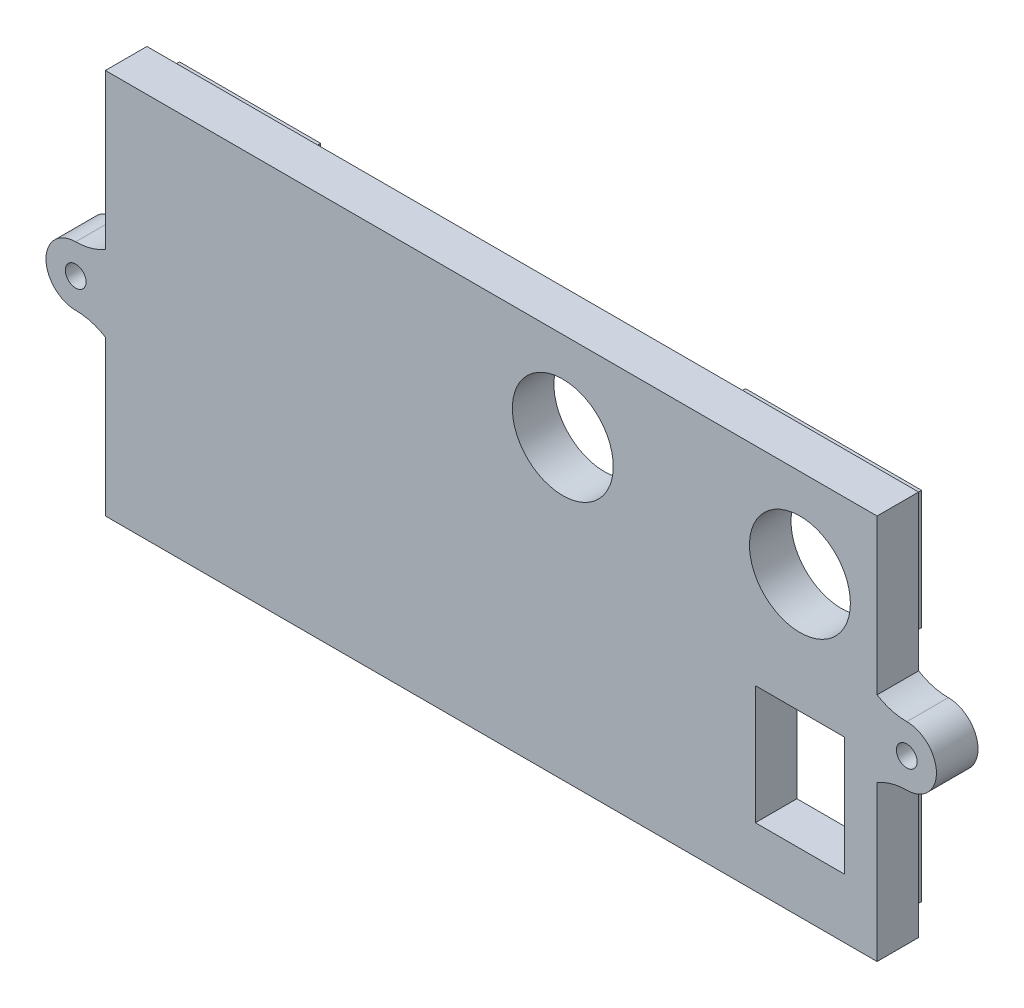
SolidWorks part; units mm, degrees
ref_plane "Front Plane" through (0, 0, 0) normal (0, 0, 1) x (1, 0, 0)
ref_plane "Top Plane" through (0, 0, 0) normal (0, 1, 0) x (1, 0, 0)
ref_plane "Right Plane" through (0, 0, 0) normal (1, 0, 0) x (0, 0, -1)
sketch "Sketch1" plane through (0, 0, 0) normal (0, 0, 1) x (1, 0, 0)
  line L0 (125.6313, -121.0524) -> (123.6313, -121.0524)
  line L1 (-1.8687, -81.4589) -> (128.1313, -81.4589)
  line L2 (-1.8687, -81.4589) -> (-1.8687, -146.4589)
  line L3 (-1.8687, -146.4589) -> (128.1313, -146.4589)
  line L4 (128.1313, -81.4589) -> (128.1313, -146.4589)
  line L5 (126.1313, -144.4589) -> (0.1313, -144.4589)
  line L6 (126.1313, -144.4589) -> (126.1313, -83.4589)
  line L7 (126.1313, -83.4589) -> (0.1313, -83.4589)
  line L8 (0.1313, -144.4589) -> (0.1313, -83.4589)
  line L9 (0.6313, -83.9589) -> (125.6313, -83.9589)
  line L10 (0.6313, -83.9589) -> (0.6313, -143.9589)
  line L11 (0.6313, -143.9589) -> (125.6313, -143.9589)
  line L12 (125.6313, -83.9589) -> (125.6313, -143.9589)
  line L13 (123.6313, -141.9589) -> (2.6313, -141.9589)
  line L14 (123.6313, -141.9589) -> (123.6313, -85.9589)
  line L15 (123.6313, -85.9589) -> (2.6313, -85.9589)
  line L16 (2.6313, -141.9589) -> (2.6313, -85.9589)
  line L17 (85.2981, -141.9589) -> (85.2981, -144.4589)
  line L18 (125.6313, -103.9925) -> (123.6313, -103.9925)
  line L19 (95.9831, -85.9589) -> (95.9831, -83.9589)
  line L20 (128.1313, -120.3642) -> (128.1313, -107.5536)
  line L21 (63.1313, -146.4589) -> (63.1313, -80.5329) construction
  line L22 (-1.8687, -120.3642) -> (-1.8687, -107.5536)
  line L23 (33.7493, -144.4589) -> (33.7493, -141.9589)
  line L24 (2.6313, -122.5906) -> (0.6313, -122.5906)
  line L25 (2.6313, -102.2391) -> (0.1313, -102.2391)
  line L26 (24.4019, -85.9589) -> (24.4019, -83.4589)
  circle A0 centre (133.1313, -113.9589) radius 1.75
  circle A1 centre (133.1313, -113.9589) radius 5
  arc A2 (128.1313, -120.3642) -> (133.1313, -118.9589) centre (133.1313, -128.5565) cw
  arc A3 (128.1313, -107.5536) -> (133.1313, -108.9589) centre (133.1313, -99.3613) ccw
  arc A4 (-1.8687, -107.5536) -> (-6.8687, -108.9589) centre (-6.8687, -99.3613) cw
  arc A5 (-1.8687, -120.3642) -> (-6.8687, -118.9589) centre (-6.8687, -128.5565) ccw
  circle A6 centre (-6.8687, -113.9589) radius 5
  circle A7 centre (-6.8687, -113.9589) radius 1.75
  dimension "D7" = 3.5
  dimension "D1" = 65
  dimension "D2" = 130
  dimension "D3" = 2
  dimension "D4" = 2
  dimension "D5" = 2
  dimension "D6" = 2
  dimension "D8" = 0.5
  dimension "D9" = 0.5
  dimension "D10" = 0.5
  dimension "D11" = 0.5
extrude "Boss-Extrude1" add sketch "Sketch1" along normal blind 7 contours L21 L13 L14 L15 | L13 L21 L15 L16 | L11 L21 L13 L23 | L21 L11 L17 L13 | L21 L3 L4 L20 L1 L7 L6 L5 | L3 L21 L5 L8 L7 L1 L2 L22 | L16 L24 L10 L11 L23 L13 | L16 L25 L10 L24 | L15 L26 L9 L10 L25 L16 | L15 L21 L9 L26 | L21 L15 L19 L9 | L19 L15 L14 L18 L12 L9 | L12 L18 L14 L0 | L13 L17 L11 L12 L0 L14 | L21 L9 L12 L11 L17 L5 L6 L7 | L21 L5 L17 L11 | L5 L21 L11 L23 | L10 L25 L8 L5 L23 L11 | L9 L26 L7 L8 L25 L10 | L9 L21 L7 L26 | L20 A2 A1 | A1 A0 | A3 L4 A1 | A6 A7 | A4 A6 L2 | L22 A6 A5 region at (125.1675, -132.5056, 0) region at (124.6313, -112.5225, 0) region at (125.719, -112.5225, 0) region at (93.3813, -113.9589, 0) region at (124.6313, -103.6347, 0) region at (74.2147, -144.2089, 0) region at (74.2147, -142.9589, 0) region at (79.5572, -84.9589, 0) region at (48.4403, -144.2089, 0) region at (48.4403, -142.9589, 0) region at (105.7147, -145.3781, 0) region at (32.8813, -113.9589, 0) region at (43.7666, -84.9589, 0) region at (43.7666, -83.7089, 0) region at (33.2096, -144.2089, 0) region at (17.1903, -143.5647, 0) region at (62.2121, -145.4589, 0) region at (24.102, -84.9589, 0) region at (12.5166, -83.652, 0) region at (1.6313, -112.4149, 0) region at (-3.0194, -118.2975, 0) region at (129.2821, -118.2975, 0) region at (-3.0194, -109.6202, 0) region at (129.2821, -109.6202, 0) region at (-3.4331, -117.3944, 0) region at (129.6958, -110.5233, 0)
extrude "Boss-Extrude3" add sketch "Sketch1<4>" against normal blind 3 contours L19 L15 L14 L18 L12 L9 | L13 L17 L11 L12 L0 L14 | L16 L24 L10 L11 L23 L13 | L15 L26 L9 L10 L25 L16 region at (125.1675, -132.5056, 0) region at (124.6313, -103.6347, 0) region at (17.1903, -143.5647, 0) region at (24.102, -84.9589, 0)
sketch "Sketch1<4>" plane through (0, 0, 0) normal (0, 0, 1) x (1, 0, 0) same geometry as "Sketch1"
sketch "Sketch2" plane through (0, 0, 7) normal (0, 0, 1) x (1, 0, 0)
  line L0 (-1.8687, -81.4589) -> (128.1313, -81.4589) construction
  line L1 (128.1313, -81.4589) -> (128.1313, -107.5536) construction
  line L2 (-1.8687, -146.4589) -> (128.1313, -146.4589) construction
  line L3 (107.6313, -116.4589) -> (122.6313, -116.4589)
  line L4 (107.6313, -116.4589) -> (107.6313, -136.4589)
  line L5 (107.6313, -136.4589) -> (122.6313, -136.4589)
  line L6 (122.6313, -116.4589) -> (122.6313, -136.4589)
  line L7 (107.6313, -116.4589) -> (122.6313, -136.4589) construction
  line L8 (107.6313, -136.4589) -> (122.6313, -116.4589) construction
  circle A0 centre (115.1313, -96.4589) radius 8.5
  circle A1 centre (75.1882, -96.4589) radius 8.5
  point P6 (115.1313, -126.4589)
  dimension "D1" = 17
  dimension "D7" = 17
  dimension "D2" = 15
  dimension "D3" = 13
  dimension "D4" = 20
  dimension "D5" = 15
  dimension "D6" = 20
extrude "Cut-Extrude1" cut sketch "Sketch2" against normal blind 23 and the other way blind 18
